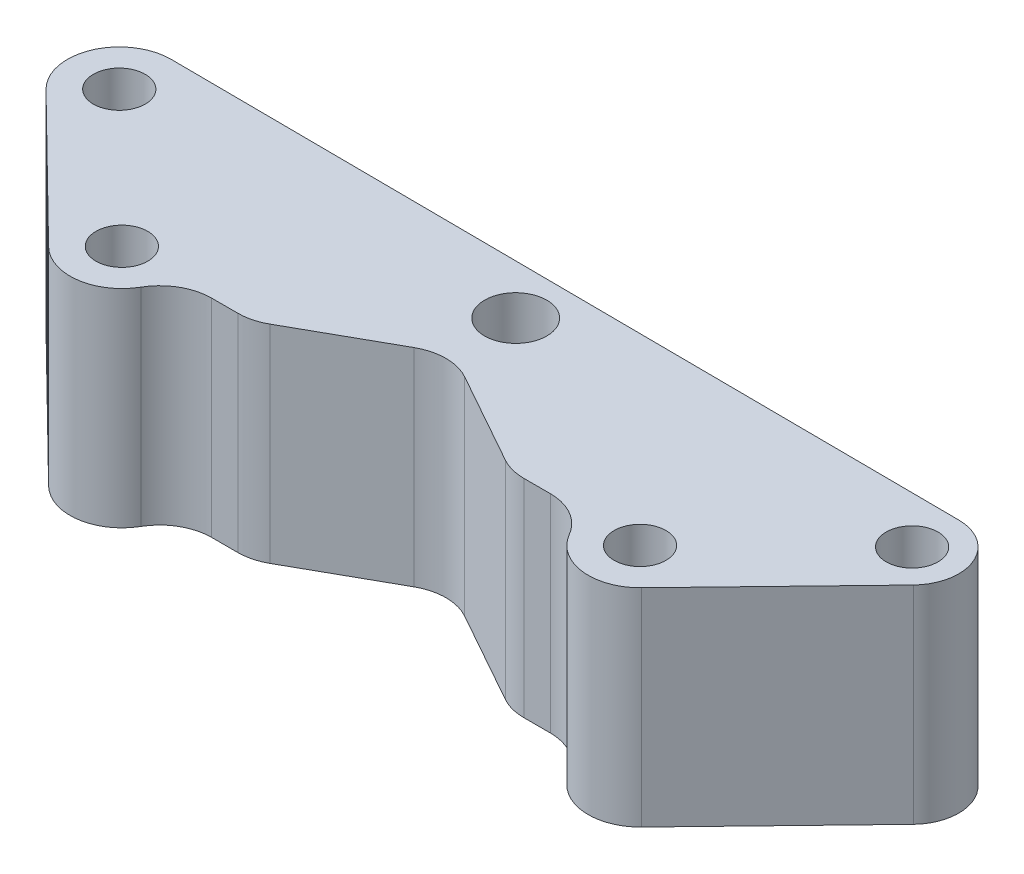
SolidWorks part; units mm, degrees
ref_plane "Płaszczyzna przednia" through (0, 0, 0) normal (0, 0, 1) x (1, 0, 0)
ref_plane "Płaszczyzna górna" through (0, 0, 0) normal (0, 1, 0) x (1, 0, 0)
ref_plane "Płaszczyzna prawa" through (0, 0, 0) normal (1, 0, 0) x (0, 0, -1)
sketch "Szkic1" plane through (0, 0, 0) normal (0, 1, 0) x (1, 0, 0)
  line L0 (-76.5, 10) -> (76.5588, 8.9998)
  line L1 (-83.5034, -7.1381) -> (-57.0034, -33.1381)
  line L2 (57.1931, -32.9469) -> (82.9738, -6.2522)
  line L3 (-50, -36) -> (50, -36)
  line L4 (-40, -26) -> (40, -26)
  circle A0 centre (-76.5, 0) radius 5
  circle A1 centre (76.5, 0) radius 5
  circle A2 centre (-76.5, 0) radius 10
  circle A3 centre (76.5, 0) radius 9
  circle A4 centre (0, 0) radius 6
  circle A5 centre (-50, -26) radius 5
  circle A6 centre (50, -26) radius 5
  circle A7 centre (-50, -26) radius 10
  circle A8 centre (50, -26) radius 10
  dimension "D1" = 10
  dimension "D2" = 10
  dimension "D7" = 12
  dimension "D8" = 10
  dimension "D9" = 100
  dimension "D3" = 153
  dimension "D4" = 76.5
  dimension "D10" = 50
  dimension "D11" = 26
  dimension "D5" = 5
  dimension "D6" = 4
  dimension "D12" = 5
extrude "Dodanie-wyciągnięcie1" add sketch "Szkic1" along normal blind 40 contours A2 A0 | A8 L2 A3 L0 A2 L1 A7 L3 A4 | A7 A5 | A8 A6 | A3 A1 region at (-0.137, 0, 7.6807) region at (-69.6289, 0, -6.8711) region at (82.7041, 0, -6.1637) region at (-53.7613, 0, 17.0403) region at (53.7966, 0, 34.9448)
sketch "Szkic2" plane through (0, 0, 0) normal (0, -1, 0) x (1, 0, 0)
  circle A0 centre (0, 0) radius 11
  dimension "D1" = 22
extrude "Wytnij-wyciągnięcie1" cut sketch "Szkic2" against normal blind 5
sketch "Szkic3" plane through (0, 5, 0) normal (0, -1, 0) x (1, 0, 0)
  line L0 (0, 0) -> (-5.6569, 5.6569) construction
  line L1 (0, 0) -> (0, 9.4855) construction
  circle A0 centre (0, 0) radius 8 construction
  circle A1 centre (-5.6569, 5.6569) radius 1.25
  circle A2 centre (5.6569, 5.6569) radius 1.25
  circle A3 centre (5.6569, -5.6569) radius 1.25
  circle A4 centre (-5.6569, -5.6569) radius 1.25
  point P15 (0, 0)
  dimension "D1" = 16
  dimension "D2" = 2.5
  dimension "D3" = 45
  dimension "D4" = 4
extrude "Wytnij-wyciągnięcie2" cut sketch "Szkic3" against normal blind 10
sketch "Szkic4" plane through (0, 40, 0) normal (0, 1, 0) x (1, 0, 0)
  line L0 (-25, -26) -> (0, -12)
  line L1 (-40, -26) -> (40, -26) construction
  line L2 (0, -12) -> (25, -26)
  line L3 (25, -26) -> (-25, -26)
  dimension "D1" = 14
  dimension "D2" = 50
extrude "Wytnij-wyciągnięcie3" cut sketch "Szkic4" against normal through all
fillet "Zaokrąglenie1" radius 10 5 edges at (40, 20, 26) (-40, 20, 26) (25, 20, 26) (0, 20, 12) (-25, 20, 26)
